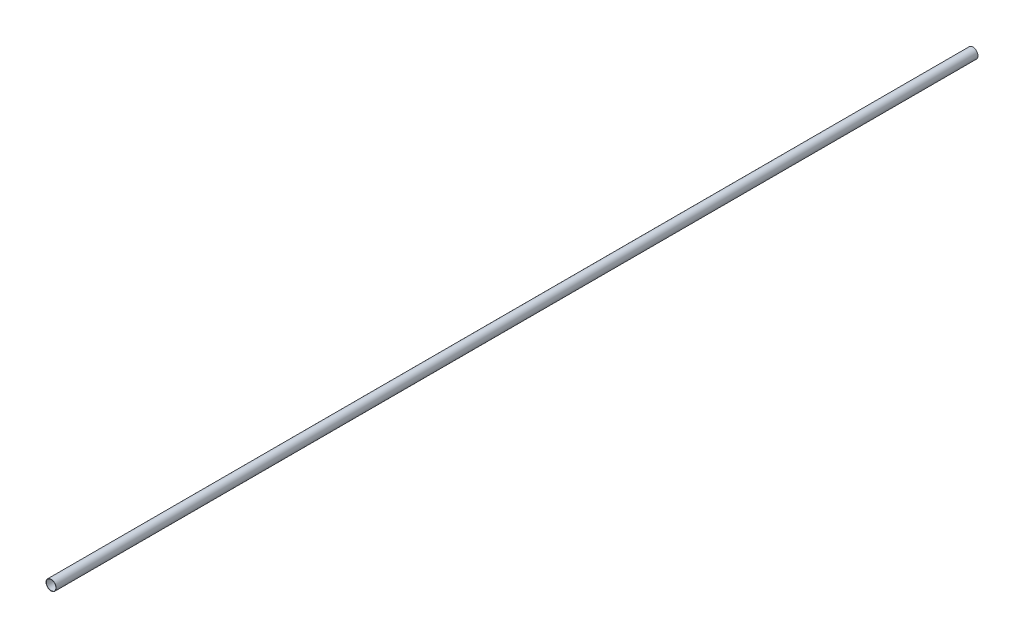
SolidWorks part; units mm, degrees
material "6061-T6 (SS)"
ref_plane "Front Plane" through (0, 0, 0) normal (0, 0, 1) x (1, 0, 0)
ref_plane "Top Plane" through (0, 0, 0) normal (0, 1, 0) x (1, 0, 0)
ref_plane "Right Plane" through (0, 0, 0) normal (1, 0, 0) x (0, 0, -1)
sketch "Sketch1" plane through (0, 0, 0) normal (0, 0, 1) x (1, 0, 0)
  circle A0 centre (-112.4828, -112.4828) radius 4.318
  circle A1 centre (-112.4828, -112.4828) radius 4.572
  dimension "D1" = 0.254
  dimension "D2" = 8.636
extrude "Boss-Extrude1" add sketch "Sketch1" along normal blind 825.5
